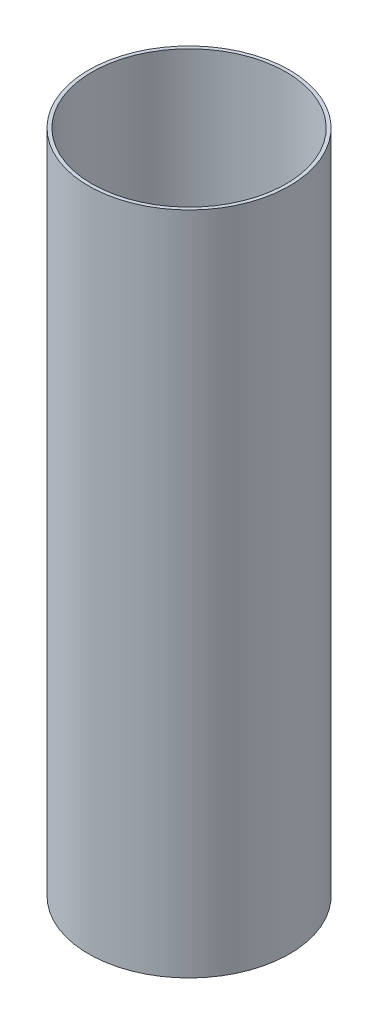
SolidWorks part; units mm, degrees
ref_plane "Front Plane" through (0, 0, 0) normal (0, 0, 1) x (1, 0, 0)
ref_plane "Top Plane" through (0, 0, 0) normal (0, 1, 0) x (1, 0, 0)
ref_plane "Right Plane" through (0, 0, 0) normal (1, 0, 0) x (0, 0, -1)
sketch "Sketch1" plane through (0, 0, 0) normal (0, 1, 0) x (1, 0, 0)
  circle A0 centre (0, 0) radius 88.9
  circle A1 centre (0, 0) radius 92.075
  dimension "D1" = 184.15
  dimension "D2" = 177.8
extrude "Boss-Extrude1" add sketch "Sketch1" along normal blind 609.6 contours A1 A0 region at (-89.4707, 0, 0)
